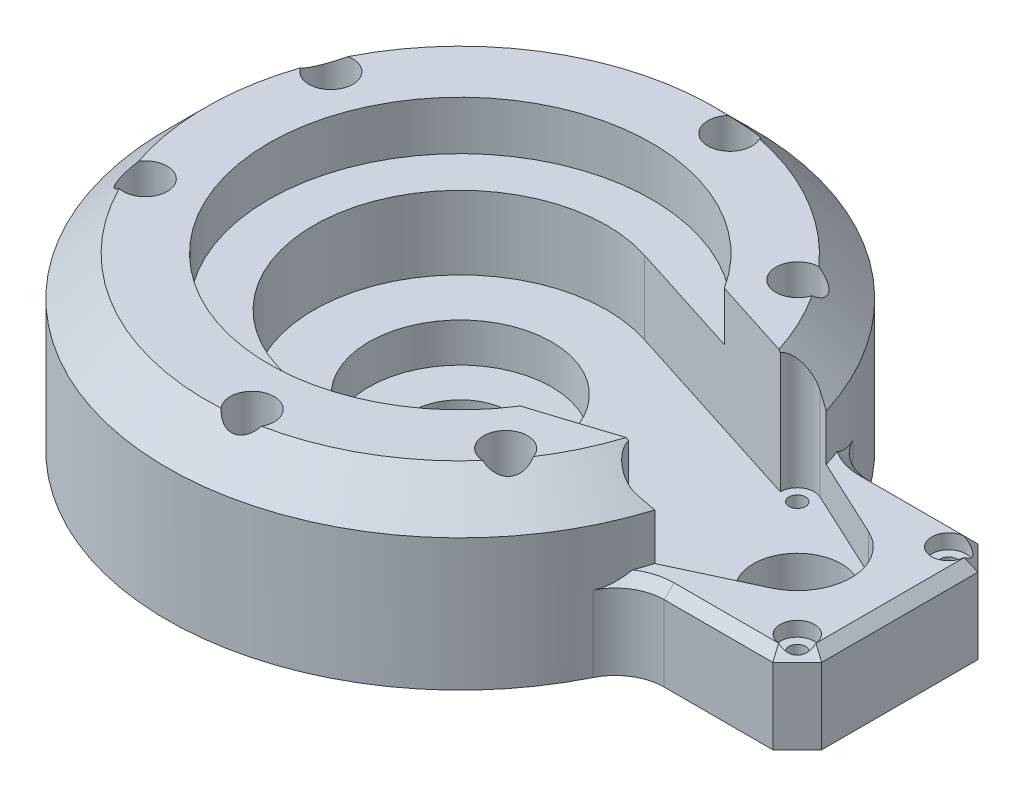
SolidWorks part; units mm, degrees
ref_plane "前视基准面" through (0, 0, 0) normal (0, 0, 1) x (1, 0, 0)
ref_plane "上视基准面" through (0, 0, 0) normal (0, 1, 0) x (1, 0, 0)
ref_plane "右视基准面" through (0, 0, 0) normal (1, 0, 0) x (0, 0, -1)
sketch "草图1" plane through (0, 0, 0) normal (0, 1, 0) x (1, 0, 0)
  circle A0 centre (0, 0) radius 60
  dimension "D1" = 120
extrude "凸台-拉伸1" add sketch "草图1" along normal blind 35
sketch "草图2" plane through (0, 35, 0) normal (0, 1, 0) x (1, 0, 0)
  line L1 (30, 21) -> (90, 21)
  line L2 (30, 21) -> (30, -21)
  line L3 (30, -21) -> (90, -21)
  line L4 (90, 21) -> (90, -21)
  line L5 (30, 21) -> (90, -21) construction
  line L6 (30, -21) -> (90, 21) construction
  circle A0 centre (0, 0) radius 60 construction
  point P0 (60, 0)
  dimension "D2" = 90
  dimension "D1" = 42
extrude "凸台-拉伸2" add sketch "草图2" against normal up to surface (35 mm away) up to face at (0, 0, 60)
chamfer "倒角1" distance 5 angle 45 2 edges at (90, 17.5, 21) (90, 17.5, -21)
sketch "草图4" plane through (0, 0, 0) normal (0, 0, 1) x (1, 0, 0)
  line L0 (90, 17.5) -> (60, 17.5)
  line L1 (90, 35) -> (90, 0) construction
  line L2 (90, 17.5) -> (104.1615, 17.5)
  line L3 (60, 17.5) -> (60, 35)
  line L4 (60, 35) -> (115.5762, 66.5338)
  line L6 (0, 0) -> (0, 35.1799) construction
  line L7 (56.205, 35) -> (85, 35) construction
  line L8 (104.1615, 17.5) -> (115.5762, 66.5338)
  dimension "D2" = 60
revolve "切除-旋转2" cut sketch "草图4" angle 360 about L6
sketch "草图5" plane through (0, 35, 0) normal (0, 1, 0) x (1, 0, 0)
  circle A0 centre (0, 0) radius 39.2
  dimension "D1" = 78.4
extrude "切除-拉伸1" cut sketch "草图5" against normal blind 10
sketch "草图6" plane through (0, 0, 0) normal (0, -1, 0) x (1, 0, 0)
  circle A0 centre (0, 0) radius 18.7
  dimension "37.4" = 37.4
extrude "切除-拉伸2" cut sketch "草图6" against normal blind 15
sketch "草图7" plane through (0, 25, 0) normal (0, 1, 0) x (1, 0, 0)
  circle A0 centre (0, 0) radius 30
  dimension "D1" = 60
extrude "切除-拉伸3" cut sketch "草图7" against normal blind 15
sketch "草图8" plane through (0, 25, 0) normal (0, 1, 0) x (1, 0, 0)
  line L0 (0, 0) -> (90, 0) construction
  line L1 (90, 16) -> (90, -16) construction
  line L2 (71.7391, 8.573) -> (9.1304, 28.5768)
  line L3 (71.7391, -8.573) -> (9.1304, -28.5768)
  arc A0 (71.7391, -8.573) -> (71.7391, 8.573) centre (69, 0) ccw
  circle A1 centre (0, 0) radius 30 construction
  arc A2 (9.1304, 28.5768) -> (9.1304, -28.5768) centre (0, 0) ccw
  dimension "D2" = 18
  dimension "D1" = 21
extrude "切除-拉伸4" cut sketch "草图8" against normal up to surface (15 mm away) and the other way blind 20 up to face at (0, 10, 30)
fillet "圆角1" radius 10 2 edges at (56.205, 8.75, 21) (56.205, 8.75, -21)
chamfer "倒角2" distance 3 angle 45 2 edges at (58.627, 26.25, -12.7625) (58.627, 26.25, 12.7625) first distance on face at (27.264, 17.5, 0)
chamfer "倒角3" distance 8 angle 45 1 edges at (-60, 35, 0)
chamfer "倒角4" distance 2 angle 45 7 edges at (57.4835, 17.5, 22.5063) (57.4835, 17.5, -22.5063) (73.8807, 17.5, -21) (87.5, 17.5, -18.5) (90, 17.5, 0) (87.5, 17.5, 18.5) (73.8807, 17.5, 21)
sketch "草图9" plane through (0, 0, 0) normal (0, -1, 0) x (1, 0, 0)
  circle A0 centre (0, 0) radius 10
  circle A2 centre (0, 0) radius 20
  dimension "D1" = 20
  dimension "D2" = 40
extrude "凸台-拉伸4" add sketch "草图9" against normal blind 2
sketch "草图11" plane through (0, 0, 0) normal (0, -1, 0) x (1, 0, 0)
  circle A0 centre (6.2955, -48.9042) radius 2.2
  circle A1 centre (39.2045, -29.9042) radius 2.2
  circle A2 centre (-45.5, -19) radius 2.2
  circle A3 centre (-45.5, 19) radius 2.2
  circle A4 centre (6.2955, 48.9042) radius 2.2
  circle A5 centre (39.2045, 29.9042) radius 2.2
  dimension "D1" = 4.4
extrude "切除-拉伸5" cut sketch "草图11" against normal through all
sketch "草图12" plane through (0, 35, 0) normal (0, 1, 0) x (1, 0, 0)
  circle A0 centre (-45.5, 19) radius 4.5
  circle A1 centre (-45.5, -19) radius 4.5
  circle A2 centre (6.2955, -48.9042) radius 4.5
  circle A3 centre (39.2045, -29.9042) radius 4.5
  circle A4 centre (39.2045, 29.9042) radius 4.5
  circle A5 centre (6.2955, 48.9042) radius 4.5
  dimension "D1" = 9
extrude "切除-拉伸6" cut sketch "草图12" against normal blind 15
sketch "草图13" plane through (0, 0, 0) normal (0, -1, 0) x (1, 0, 0)
  circle A0 centre (84.5, -15.5) radius 1.7
  circle A1 centre (53.5, -15.5) radius 1.7
  circle A2 centre (84.5, 15.5) radius 1.7
  circle A3 centre (53.5, 15.5) radius 1.7
  dimension "D1" = 3.4
extrude "切除-拉伸7" cut sketch "草图13" against normal through all
sketch "草图16" plane through (0, 35, 0) normal (0, 1, 0) x (1, 0, 0)
  line L0 (54.9787, -18.6723) -> (73.6474, -9.97)
  line L1 (54.9787, 18.6723) -> (73.6474, 9.97)
  line L2 (50, -15.5) -> (50, 15.5)
  circle A0 centre (69, 0) radius 11
  circle A2 centre (0, 0) radius 3.4844
  circle A3 centre (53.5, -15.5) radius 3.5
  circle A4 centre (53.5, 15.5) radius 3.5
  dimension "D1" = 22
  dimension "D2" = 7
  dimension "D3" = 7
extrude "切除-拉伸11" cut sketch "草图16" against normal up to surface (25 mm away) contours A3 | A4 | A4 L2 A3 L0 A0 L1 | A0 region at (57.1275, 35, 0) region at (53.5, 35, 15.5) region at (69, 35, 0) region at (53.5, 35, -15.5) up to face at (42.6497, 10, 0)
sketch "草图17" plane through (0, 17.5, 0) normal (0, 1, 0) x (1, 0, 0)
  circle A0 centre (84.5, -15.5) radius 3.5
  circle A1 centre (84.5, 15.5) radius 3.5
  dimension "D1" = 7
  dimension "D2" = 7
extrude "切除-拉伸12" cut sketch "草图17" against normal blind 3
sketch "草图19" plane through (0, 10, 0) normal (0, 1, 0) x (1, 0, 0)
  circle A0 centre (69, 0) radius 9
  dimension "D1" = 18
extrude "切除-拉伸13" cut sketch "草图19" against normal through all
sketch "草图21" plane through (0, 0, 0) normal (0, -1, 0) x (1, 0, 0)
  circle A0 centre (69, 0) radius 11.1
  dimension "D1" = 22.2
extrude "切除-拉伸14" cut sketch "草图21" against normal blind 2.2
